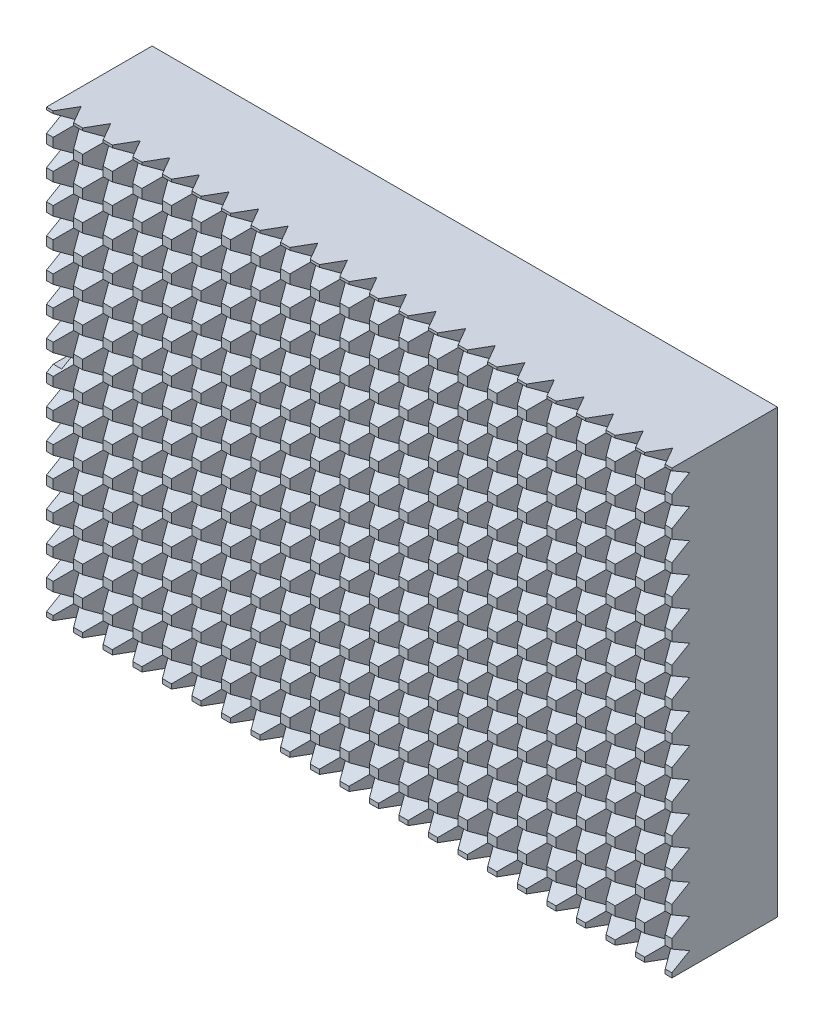
SolidWorks part; units mm, degrees
ref_plane "前视基准面" through (0, 0, 0) normal (0, 0, 1) x (1, 0, 0)
ref_plane "上视基准面" through (0, 0, 0) normal (0, 1, 0) x (1, 0, 0)
ref_plane "右视基准面" through (0, 0, 0) normal (1, 0, 0) x (0, 0, -1)
other "Configuration Table"
sketch "草图1" plane through (0, 0, 0) normal (0, 1, 0) x (1, 0, 0)
  line L1 (0, 0) -> (148, 0)
  line L2 (0, 0) -> (0, 25)
  line L3 (0, 25) -> (148, 25)
  line L4 (148, 0) -> (148, 25)
extrude "凸台-拉伸1" add sketch "草图1" along normal blind 105
sketch "草图2" plane through (0, 0, 0) normal (-1, 0, 0) x (0, 0, 1)
  line L0 (0, 0) -> (-10, 0)
  line L2 (-25, 0) -> (0, 0) construction
  line L3 (-10, 0) -> (-10, 34)
  line L4 (-10, 34) -> (-10, 37)
  circle A1 centre (-10, 37) radius 2.98
extrude "切除-拉伸1" cut sketch "草图2" against normal blind 100 contours A1 region at (0, 34.9524, -7.9524)
sketch "草图3" plane through (0, 0, 0) normal (0, -1, 0) x (1, 0, 0)
  line L0 (140, 1) -> (137, -4.1962)
  line L1 (134, 1) -> (137, -4.1962)
  line L2 (140, 1) -> (134, 1)
  line L4 (147, 1) -> (141, 1)
  line L5 (141, 1) -> (144, -4.1962)
  line L6 (147, 1) -> (144, -4.1962)
  line L7 (133, 1) -> (130, -4.1962)
  line L8 (127, 1) -> (130, -4.1962)
  line L9 (133, 1) -> (127, 1)
  line L10 (126, 1) -> (123, -4.1962)
  line L11 (120, 1) -> (123, -4.1962)
  line L12 (126, 1) -> (120, 1)
  line L13 (119, 1) -> (116, -4.1962)
  line L14 (113, 1) -> (116, -4.1962)
  line L15 (119, 1) -> (113, 1)
  line L16 (112, 1) -> (109, -4.1962)
  line L17 (106, 1) -> (109, -4.1962)
  line L18 (112, 1) -> (106, 1)
  line L19 (105, 1) -> (102, -4.1962)
  line L20 (99, 1) -> (102, -4.1962)
  line L21 (105, 1) -> (99, 1)
  line L22 (98, 1) -> (95, -4.1962)
  line L23 (92, 1) -> (95, -4.1962)
  line L24 (98, 1) -> (92, 1)
  line L25 (91, 1) -> (88, -4.1962)
  line L26 (85, 1) -> (88, -4.1962)
  line L27 (91, 1) -> (85, 1)
  line L28 (84, 1) -> (81, -4.1962)
  line L29 (78, 1) -> (81, -4.1962)
  line L30 (84, 1) -> (78, 1)
  line L31 (77, 1) -> (74, -4.1962)
  line L32 (71, 1) -> (74, -4.1962)
  line L33 (77, 1) -> (71, 1)
  line L34 (70, 1) -> (67, -4.1962)
  line L35 (64, 1) -> (67, -4.1962)
  line L36 (70, 1) -> (64, 1)
  line L37 (63, 1) -> (60, -4.1962)
  line L38 (57, 1) -> (60, -4.1962)
  line L39 (63, 1) -> (57, 1)
  line L40 (56, 1) -> (53, -4.1962)
  line L41 (50, 1) -> (53, -4.1962)
  line L42 (56, 1) -> (50, 1)
  line L43 (49, 1) -> (46, -4.1962)
  line L44 (43, 1) -> (46, -4.1962)
  line L45 (49, 1) -> (43, 1)
  line L46 (42, 1) -> (39, -4.1962)
  line L47 (36, 1) -> (39, -4.1962)
  line L48 (42, 1) -> (36, 1)
  line L49 (35, 1) -> (32, -4.1962)
  line L50 (29, 1) -> (32, -4.1962)
  line L51 (35, 1) -> (29, 1)
  line L52 (28, 1) -> (25, -4.1962)
  line L53 (22, 1) -> (25, -4.1962)
  line L54 (28, 1) -> (22, 1)
  line L55 (21, 1) -> (18, -4.1962)
  line L56 (15, 1) -> (18, -4.1962)
  line L57 (21, 1) -> (15, 1)
  line L58 (14, 1) -> (11, -4.1962)
  line L59 (8, 1) -> (11, -4.1962)
  line L60 (14, 1) -> (8, 1)
  line L61 (7, 1) -> (4, -4.1962)
  line L62 (1, 1) -> (4, -4.1962)
  line L63 (7, 1) -> (1, 1)
  dimension "D1" = 21
extrude "切除-拉伸2" cut sketch "草图3" against normal blind 105
sketch "草图4" plane through (0, 0, 0) normal (-1, 0, 0) x (0, 0, 1)
  line L0 (0, 105) -> (1, 105)
  line L1 (1, 105) -> (1, 99)
  line L5 (-4.1962, 102) -> (1, 105)
  line L6 (1, 99) -> (-4.1962, 102)
  line L7 (1, 98) -> (1, 92)
  line L8 (1, 92) -> (-4.1962, 95)
  line L9 (-4.1962, 95) -> (1, 98)
  line L10 (1, 91) -> (1, 85)
  line L11 (1, 85) -> (-4.1962, 88)
  line L12 (-4.1962, 88) -> (1, 91)
  line L13 (1, 84) -> (1, 78)
  line L14 (1, 78) -> (-4.1962, 81)
  line L15 (-4.1962, 81) -> (1, 84)
  line L16 (1, 77) -> (1, 71)
  line L17 (1, 71) -> (-4.1962, 74)
  line L18 (-4.1962, 74) -> (1, 77)
  line L19 (1, 70) -> (1, 64)
  line L20 (1, 64) -> (-4.1962, 67)
  line L21 (-4.1962, 67) -> (1, 70)
  line L22 (1, 63) -> (1, 57)
  line L23 (1, 57) -> (-4.1962, 60)
  line L24 (-4.1962, 60) -> (1, 63)
  line L25 (1, 56) -> (1, 50)
  line L26 (1, 50) -> (-4.1962, 53)
  line L27 (-4.1962, 53) -> (1, 56)
  line L28 (1, 49) -> (1, 43)
  line L29 (1, 43) -> (-4.1962, 46)
  line L30 (-4.1962, 46) -> (1, 49)
  line L31 (1, 42) -> (1, 36)
  line L32 (1, 36) -> (-4.1962, 39)
  line L33 (-4.1962, 39) -> (1, 42)
  line L34 (1, 35) -> (1, 29)
  line L35 (1, 29) -> (-4.1962, 32)
  line L36 (-4.1962, 32) -> (1, 35)
  line L37 (1, 28) -> (1, 22)
  line L38 (1, 22) -> (-4.1962, 25)
  line L39 (-4.1962, 25) -> (1, 28)
  line L40 (1, 21) -> (1, 15)
  line L41 (1, 15) -> (-4.1962, 18)
  line L42 (-4.1962, 18) -> (1, 21)
  line L43 (1, 14) -> (1, 8)
  line L44 (1, 8) -> (-4.1962, 11)
  line L45 (-4.1962, 11) -> (1, 14)
  line L46 (1, 7) -> (1, 1)
  line L47 (1, 1) -> (-4.1962, 4)
  line L48 (-4.1962, 4) -> (1, 7)
  line M11 (0, 0) -> (0, 105)
  dimension "D1" = 15
extrude "切除-拉伸3" cut sketch "草图4" against normal blind 148 contours L6 L5 M11 | L9 L8 M11 | L12 L11 M11 | L15 L14 M11 | L18 L17 M11 | L21 L20 M11 | L24 L23 M11 | L27 L26 M11 | L30 L29 M11 | L33 L32 M11 | L36 L35 M11 | L39 L38 M11 | L42 L41 M11 | L45 L44 M11 | L48 L47 M11 region at (0, 4, -1.3987) region at (0, 11, -1.3987) region at (0, 18, -1.3987) region at (0, 25, -1.3987) region at (0, 32, -1.3987) region at (0, 39, -1.3987) region at (0, 46, -1.3987) region at (0, 53, -1.3987) region at (0, 60, -1.3987) region at (0, 67, -1.3987) region at (0, 74, -1.3987) region at (0, 81, -1.3987) region at (0, 88, -1.3987) region at (0, 95, -1.3987) region at (0, 102, -1.3987)
sketch "草图5" plane through (0, 0, 0) normal (-1, 0, 0) x (0, 0, 1)
  line L8 (-17.5, 53.5) -> (0, 53.5)
  line L9 (0, 53.5) -> (0, 51.5)
  line L10 (0, 51.5) -> (-25, 51.5)
  line L11 (-25, 51.5) -> (-25, 53.5)
  line L12 (-25, 53.5) -> (-17.5, 53.5)
extrude "切除-拉伸4" cut sketch "草图5" against normal blind 2
sketch "草图6" plane through (0, 0, 0) normal (-1, 0, 0) x (0, 0, 1)
  line L0 (0, 1.5774) -> (0, 0) construction
  line L1 (-25, 0) -> (0, 0)
  line L2 (-25, 0) -> (-25, 0.5)
  line L3 (-25, 0.5) -> (0, 0.5)
  line L4 (0, 0) -> (0, 0.5)
extrude "切除-拉伸5" cut sketch "草图6" against normal blind 500
